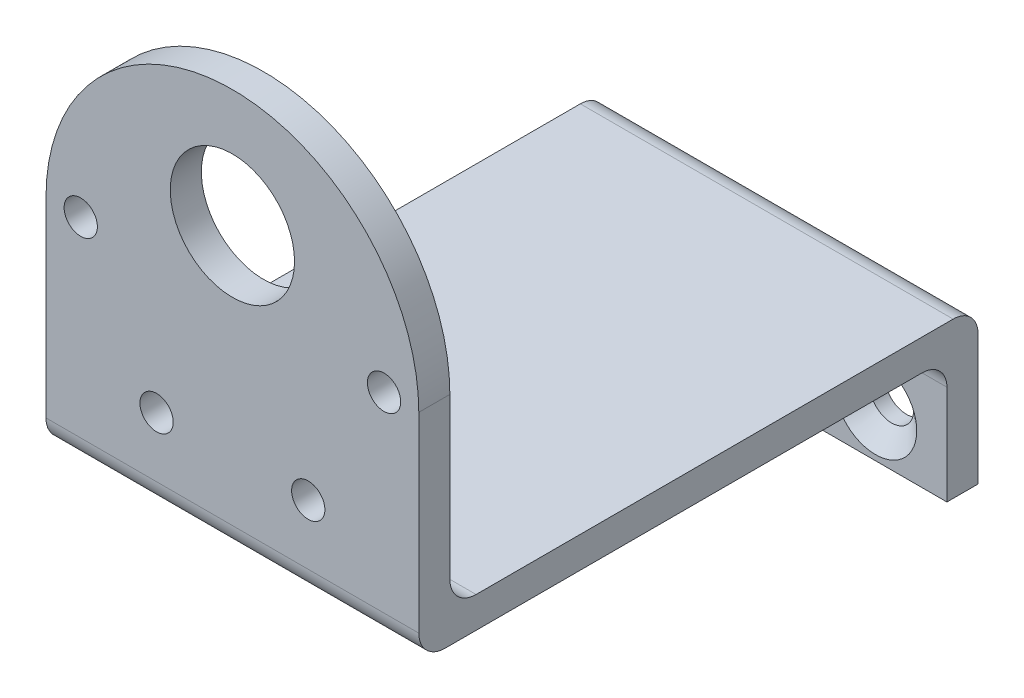
SolidWorks part; units mm, degrees
ref_plane "Front Plane" through (0, 0, 0) normal (0, 0, 1) x (1, 0, 0)
ref_plane "Top Plane" through (0, 0, 0) normal (0, 1, 0) x (1, 0, 0)
ref_plane "Right Plane" through (0, 0, 0) normal (1, 0, 0) x (0, 0, -1)
sketch "Sketch1" plane through (0, 0, 0) normal (1, 0, 0) x (0, 0, -1)
  line L0 (0, 42.0944) -> (0, 6.6753)
  line L1 (2.681, 3.9944) -> (51.435, 3.9944)
  line L3 (0, 42.0944) -> (-3.175, 42.0944)
  line L4 (-3.175, 42.0944) -> (-3.175, 3.5003)
  line L5 (-0.494, 0.8194) -> (48.26, 0.8194)
  line L8 (53.975, 1.4544) -> (53.975, -11.8806)
  line L9 (53.975, -11.8806) -> (50.8, -11.8806)
  line L10 (50.8, -11.8806) -> (50.8, -1.7206)
  arc A2 (-3.175, 3.5003) -> (-0.494, 0.8194) centre (-0.494, 3.5003) ccw
  arc A3 (0, 6.6753) -> (2.681, 3.9944) centre (2.681, 6.6753) ccw
  arc A4 (51.435, 3.9944) -> (53.975, 1.4544) centre (51.435, 1.4544) cw
  arc A5 (48.26, 0.8194) -> (50.8, -1.7206) centre (48.26, -1.7206) cw
  point P14 (52.3875, -11.8806)
  dimension "D2" = 2.54
  dimension "D1" = 3.175
  dimension "D3" = 3.175
  dimension "D4" = 12.7
  dimension "D6" = 57.15
  dimension "D7" = 3.175
  dimension "D5" = 38.1
extrude "Boss-Extrude1" add sketch "Sketch1" along normal blind 38.1 contours L0 A3 L1 A4 L8 L9 L10 A5 L5 A2 L4 L3
hole_wizard "CSK for #8 Flat Head Machine Screw (100)2" positions "Sketch9" profile "Sketch10" countersink size "#8" standard "ANSI Inch" end condition through all
sketch "Sketch9" plane through (0, 0, -50.8) normal (0, 0, 1) x (1, 0, 0)
  line L0 (38.1, -11.8806) -> (0, -11.8806) construction
  point P0 (7.3025, -7.1181)
  point P2 (30.7975, -7.1181)
  point P7 (19.05, -11.8806)
  dimension "D1" = 23.495
  dimension "D2" = 4.7625
  dimension "D3" = 11.7475
sketch "Sketch10" plane through (7.3025, -7.1181, -50.8) normal (1, 0, 0) x (0, -1, 0)
  line L0 (0, 0) -> (0, 3.175)
  line L1 (0, 3.175) -> (2.2479, 3.175)
  line L2 (2.2479, 3.175) -> (2.2479, 1.6518)
  line L3 (2.2479, 1.6518) -> (4.2164, 0)
  line L5 (4.2164, 0) -> (0, 0)
  line L6 (-2.2479, 1.6518) -> (-4.2164, 0) construction
  line L11 (0, -6.35) -> (0, 107.95) construction
  dimension "Thru Hole Dia." = 4.4958
  dimension "Thru Hole Depth" = 3.175
  dimension "Near C'Sink Dia." = 8.4328
  dimension "Near C'Sink Angle" = 100
sketch "Sketch11" plane through (0, 0, 3.175) normal (0, 0, 1) x (1, 0, 0)
  line L0 (38.1, 42.0944) -> (0, 42.0944) construction
  line L1 (38.1, 42.0944) -> (38.1, 3.5003) construction
  line L4 (0, 23.0444) -> (0, 42.0944)
  line L5 (0, 42.0944) -> (38.1, 42.0944)
  line L6 (38.1, 23.0444) -> (38.1, 42.0944)
  arc A0 (38.1, 23.0444) -> (0, 23.0444) centre (19.05, 23.0444) ccw
  circle A3 centre (19.05, 30.0444) radius 6.35
  point P5 (19.05, 42.0944)
  line M2 (0, 42.0944) -> (0, 3.5003)
  line M4 (38.1, 3.5003) -> (38.1, 42.0944)
  line M5 (38.1, 42.0944) -> (0, 42.0944)
  dimension "D2" = 7
  dimension "D1" = 12.7
extrude "Cut-Extrude1" cut sketch "Sketch11" against normal through all contours A0 M4 M5 | A0 L5 M2 | A3 | A3 region at (33.8448, 37.8392, 3.175) region at (4.2552, 37.8392, 3.175) region at (19.05, 30.0444, 3.175)
sketch "Sketch12" plane through (0, 0, 3.175) normal (0, 0, 1) x (1, 0, 0)
  circle A0 centre (19.05, 23.0444) radius 15.5 construction
  point P3 (3.55, 23.0444)
  point P6 (11.3, 9.621)
  point P7 (26.8, 9.621)
  point P8 (34.55, 23.0444)
  point P9 (26.8, 36.4678)
  point P10 (11.3, 36.4678)
  point P11 (19.05, 23.0444)
  dimension "D1" = 31
  dimension "D2" = 6
hole_wizard "M3 Clearance Hole1" positions "Sketch13" profile "Sketch14" hole size "M3" standard "ANSI Metric" end condition through all
sketch "Sketch13" plane through (0, 0, 3.175) normal (0, 0, 1) x (1, 0, 0)
  point P0 (3.55, 23.0444)
  point P9 (34.55, 23.0444)
  point P12 (26.8, 9.621)
  point P15 (11.3, 9.621)
sketch "Sketch14" plane through (3.55, 23.0444, 3.175) normal (1, 0, 0) x (0, -1, 0)
  line L0 (0, 0) -> (0, 57.15)
  line L1 (0, 57.15) -> (1.7, 57.15)
  line L2 (1.7, 57.15) -> (1.7, 0)
  line L5 (1.7, 0) -> (0, 0)
  line L11 (0, -6.35) -> (0, 107.95) construction
  dimension "Thru Hole Dia." = 3.4
  dimension "Thru Hole Depth" = 57.15
ref_plane "Plane1" through (19.05, 0, 0) normal (1, 0, 0) x (0, 0, -1)
equation "\"D3@Sketch1\"=\"D1@Sketch1\""
equation "\"D7@Sketch1\"=\"D1@Sketch1\""
equation "\"D3@Sketch9\"=\"D1@Sketch9\"/2"
